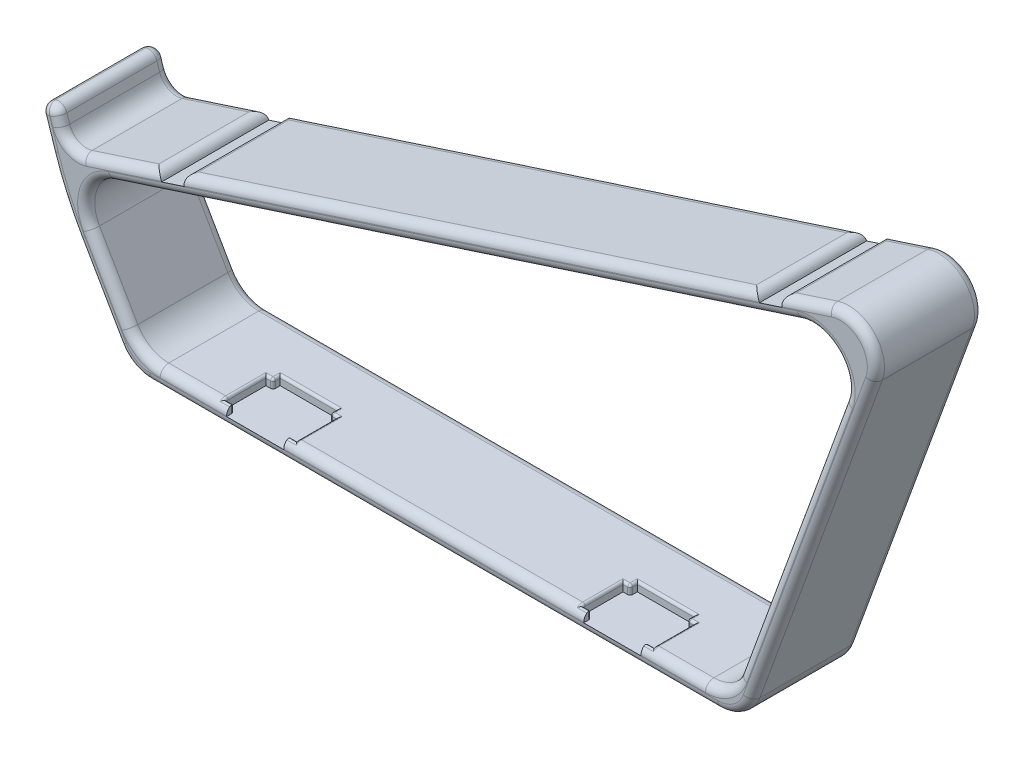
SolidWorks part; units mm, degrees
ref_plane "Front Plane" through (0, 0, 0) normal (0, 0, 1) x (1, 0, 0)
ref_plane "Top Plane" through (0, 0, 0) normal (0, 1, 0) x (1, 0, 0)
ref_plane "Right Plane" through (0, 0, 0) normal (1, 0, 0) x (0, 0, -1)
ref_axis "X Axis" through (0, 0, -132.1637) along (0, 0, 1)
ref_axis "Z Axis" through (0, -24.397, 0) along (0, 1, 0)
ref_axis "Y Axis" through (133.8141, 0, 0) along (-1, 0, 0)
sketch "Sketch13" plane through (0, 0, 0) normal (0, 0, 1) x (1, 0, 0)
  line L0 (-98.9778, 0) -> (72.8295, 0)
  line L1 (72.8295, 0) -> (116.5059, 120)
  line L2 (116.5059, 120) -> (-116.5059, 44.3)
  line L3 (-116.5059, 44.3) -> (-119.5957, 53.8107)
  line L4 (-119.5957, 53.8107) -> (-124.3511, 52.2658)
  line L5 (-124.3511, 52.2658) -> (-118.1715, 33.2444)
  line L6 (-118.1715, 33.2444) -> (-98.9778, 0)
  line L7 (-115.8657, 39.2507) -> (108.3014, 112.0773)
  line L8 (108.3014, 112.0773) -> (69.3284, 5)
  line L9 (69.3284, 5) -> (-96.091, 5)
  line L10 (-96.091, 5) -> (-115.8657, 39.2507)
  line L11 (-8.8901, 79.2618) -> (-7.3452, 74.5065) construction
  line L12 (92.7283, 69.2907) -> (97.4268, 67.5806) construction
  line L13 (33.746, 5) -> (33.746, 0) construction
  line L14 (-110.3349, 19.671) -> (-106.0047, 22.171) construction
  line L15 (116.5059, 120) -> (116.5059, 0) construction
  line L16 (116.5059, 0) -> (72.8295, 0) construction
  line L17 (-116.5059, 44.3) -> (-116.5059, 0) construction
  line L18 (-116.5059, 0) -> (-98.9778, 0) construction
  line L19 (-116.5059, 0) -> (-116.5059, -10.091) construction
  line L20 (-116.5059, -10.091) -> (116.5059, -10.091) construction
  line L21 (116.5059, -10.091) -> (116.5059, 0) construction
  line L22 (0, -10.091) -> (0, 0) construction
  dimension "D2" = 245
  dimension "D3" = 5
  dimension "D4" = 5
  dimension "D5" = 5
  dimension "D6" = 5
  dimension "D7" = 44.3
  dimension "D8" = 120
  dimension "D9" = 110
  dimension "D10" = 5
  dimension "D11" = 120
  dimension "D12" = 10
  dimension "D13" = 20
extrude "Boss-Extrude1" add sketch "Sketch13" along normal blind 30
fillet "Fillet1" radius 10 7 edges at (116.5059, 120, 15) (108.3014, 112.0773, 15) (-115.8657, 39.2507, 15) (-98.9778, 0, 15) (-96.091, 5, 15) (72.8295, 0, 15) (69.3284, 5, 15)
fillet "Fillet2" radius 90 1 edges at (-118.1715, 33.2444, 15)
fillet "Fillet3" radius 2.5 2 edges at (-119.5957, 53.8107, 15) (-124.3511, 52.2658, 15)
fillet "Fillet4" radius 5 1 edges at (-116.5059, 44.3, 15)
fillet "Fillet6" radius 2.4 42 edges at (68.0621, 6.8085, 0) (-13.9956, 5, 0) (-95.3175, 6.3397, 0) (-104.3344, 19.2779, 0) (-110.3665, 37.1397, 0) (-7.659, 74.4045, 0) (99.0859, 103.1784, 0) (86.5063, 52.1958, 0) (-122.3367, 46.0654, 0) (-117.7184, 33.4461, 0) (-107.6527, 15.0254, 0) (-98.2043, 1.3397, 0) (-13.6884, 0, 0) (71.5632, 1.8085, 0) (92.3591, 53.6571, 0) (107.2904, 111.1011, 0) (-7.3717, 79.7551, 0) (-115.5656, 46.1453, 0) (-118.437, 50.2442, 0) (-120.0659, 52.888, 0) (-123.4284, 51.7956, 0) (-95.3175, 6.3397, 30) (-13.9956, 5, 30) (68.0621, 6.8085, 30) (86.5063, 52.1958, 30) (99.0859, 103.1784, 30) (-7.659, 74.4045, 30) (-110.3665, 37.1397, 30) (-104.3344, 19.2779, 30) (107.2904, 111.1011, 30) (92.3591, 53.6571, 30) (71.5632, 1.8085, 30) (-13.6884, 0, 30) (-98.2043, 1.3397, 30) (-107.6527, 15.0254, 30) (-117.7184, 33.4461, 30) (-122.3367, 46.0654, 30) (-123.4284, 51.7956, 30) (-120.0659, 52.888, 30) (-118.437, 50.2442, 30) (-115.5656, 46.1453, 30) (-7.3717, 79.7551, 30)
sketch "Sketch17" plane through (0, 0, 0) normal (0, -1, 0) x (1, 0, 0)
  line L0 (-13.6884, 27.6) -> (-13.6884, 2.4) construction
  line L1 (65.8274, 27.6) -> (-93.2043, 27.6) construction
  line L2 (-93.2043, 2.4) -> (65.8274, 2.4) construction
  line L3 (-76.9543, 15) -> (49.5774, 15) construction
  line L4 (-93.2043, 27.6) -> (-93.2043, 2.4) construction
  line L5 (-89.4543, 2.5) -> (-64.4543, 2.5)
  line L6 (-89.4543, 2.5) -> (-89.4543, 27.5)
  line L7 (-89.4543, 27.5) -> (-64.4543, 27.5)
  line L8 (-64.4543, 2.5) -> (-64.4543, 27.5)
  line L9 (-89.4543, 2.5) -> (-64.4543, 27.5) construction
  line L10 (-89.4543, 27.5) -> (-64.4543, 2.5) construction
  line L11 (37.0774, 2.5) -> (62.0774, 2.5)
  line L12 (37.0774, 2.5) -> (37.0774, 27.5)
  line L13 (37.0774, 27.5) -> (62.0774, 27.5)
  line L14 (62.0774, 2.5) -> (62.0774, 27.5)
  line L15 (37.0774, 2.5) -> (62.0774, 27.5) construction
  line L16 (37.0774, 27.5) -> (62.0774, 2.5) construction
  point P8 (-13.6884, 15)
  point P9 (-13.6884, 15)
  dimension "D1" = 25
  dimension "D2" = 25
  dimension "D3" = 3.75
extrude "Cut-Extrude4" cut sketch "Sketch17" against normal blind 1
sketch "Sketch15" plane through (-24.1407, 74.3073, 0) normal (-0.309, 0.9511, 0) x (0.9511, 0.309, 0)
  line L0 (-97.1173, -2.4) -> (-97.1173, -27.6) construction
  line L1 (-97.1173, -15) -> (-66.6173, -15) construction
  line L2 (127.3807, -30) -> (-92.1173, -30) construction
  line L3 (-69.9673, -30) -> (-63.2673, -30)
  line L4 (-69.9673, -30) -> (-69.9673, 0)
  line L5 (-69.9673, 0) -> (-63.2673, 0)
  line L6 (-63.2673, -30) -> (-63.2673, 0)
  line L7 (-69.9673, -30) -> (-63.2673, 0) construction
  line L8 (-69.9673, 0) -> (-63.2673, -30) construction
  line L9 (-66.6173, -15) -> (109.3827, -15) construction
  line L10 (-92.1173, 0) -> (127.3807, 0) construction
  line L11 (106.0327, -30) -> (112.7327, -30)
  line L12 (106.0327, -30) -> (106.0327, 0)
  line L13 (106.0327, 0) -> (112.7327, 0)
  line L14 (112.7327, -30) -> (112.7327, 0)
  line L15 (106.0327, -30) -> (112.7327, 0) construction
  line L16 (106.0327, 0) -> (112.7327, -30) construction
  dimension "D1" = 30.5
  dimension "D2" = 6.7
  dimension "D3" = 176
extrude "Cut-Extrude2" cut sketch "Sketch15" against normal blind 2.5
sketch "Sketch16" plane through (0, 0, 30) normal (0, 0, 1) x (1, 0, 0)
  line L0 (74.326, 106.2968) -> (75.0985, 103.9191) construction
  line L1 (-84.3122, 54.759) -> (76.7037, 107.0692) construction
  line L2 (75.0985, 103.9191) -> (77.4761, 104.6915) construction
  line L4 (-104.8621, 45.349) -> (88.061, 108.0252) construction
  line L5 (74.326, 106.2968) -> (76.7037, 107.0692)
  line L6 (76.7037, 107.0692) -> (77.4761, 104.6915)
  line L7 (77.4761, 104.6915) -> (83.8483, 106.7617) construction
  line L8 (80.6622, 105.7266) -> (79.8796, 108.1354) construction
  line L9 (83.0758, 109.1394) -> (83.8483, 106.7617)
  line L10 (85.4535, 109.9118) -> (83.0758, 109.1394)
  line L11 (-83.5398, 52.3813) -> (77.4761, 104.6915) construction
  line L12 (-3.0318, 78.5364) -> (-5.2501, 85.3645) construction
  line L13 (-90.6844, 52.6888) -> (-89.9119, 50.3111)
  line L14 (-93.0621, 51.9163) -> (-90.6844, 52.6888)
  line L15 (-81.9346, 55.5314) -> (-84.3122, 54.759)
  line L16 (-84.3122, 54.759) -> (-83.5398, 52.3813)
  arc A0 (74.326, 106.2968) -> (77.4761, 104.6915) centre (75.0985, 103.9191) cw
  arc A1 (85.4535, 109.9118) -> (83.8483, 106.7617) centre (86.226, 107.5341) ccw
  arc A2 (-93.0621, 51.9163) -> (-89.9119, 50.3111) centre (-92.2896, 49.5387) cw
  arc A3 (-81.9346, 55.5314) -> (-83.5398, 52.3813) centre (-81.1621, 53.1537) ccw
  dimension "D1" = 2.5
extrude "Cut-Extrude3" cut sketch "Sketch16" against normal up to surface (30 mm away) up to face at (-33.182, 55.8128, 0)
sketch "Sketch14" plane through (0, 5, 0) normal (0, 1, 0) x (1, 0, 0)
  line L0 (-13.7135, 0) -> (-13.7135, -30) construction
  line L1 (-90.3175, -30) -> (62.3264, -30) construction
  line L2 (-63.7135, -15) -> (36.2865, -15) construction
  line L3 (-63.7135, -15) -> (-63.7135, -30) construction
  line L4 (-73.7135, -30) -> (-53.7135, -30)
  line L5 (-73.7135, -30) -> (-73.7135, -15)
  line L6 (-73.7135, -15) -> (-53.7135, -15)
  line L7 (-53.7135, -30) -> (-53.7135, -15)
  line L8 (-73.7135, -28) -> (-71.7135, -28)
  line L9 (-71.7135, -28) -> (-71.7135, -30)
  line L10 (-73.7135, -22.5) -> (-53.7135, -22.5) construction
  line L11 (-55.7135, -28) -> (-55.7135, -30)
  line L12 (-53.7135, -28) -> (-55.7135, -28)
  line L13 (-53.7135, -17) -> (-55.7135, -17)
  line L14 (-55.7135, -17) -> (-55.7135, -15)
  line L15 (-71.7135, -17) -> (-71.7135, -15)
  line L16 (-73.7135, -17) -> (-71.7135, -17)
  line L17 (28.2865, -17) -> (28.2865, -15)
  line L18 (26.2865, -17) -> (28.2865, -17)
  line L19 (26.2865, -28) -> (28.2865, -28)
  line L20 (28.2865, -28) -> (28.2865, -30)
  line L21 (44.2865, -28) -> (44.2865, -30)
  line L22 (46.2865, -28) -> (44.2865, -28)
  line L23 (44.2865, -17) -> (44.2865, -15)
  line L24 (46.2865, -17) -> (44.2865, -17)
  line L25 (46.2865, -15) -> (26.2865, -15)
  line L26 (26.2865, -30) -> (26.2865, -15)
  line L27 (46.2865, -30) -> (26.2865, -30)
  line L28 (46.2865, -30) -> (46.2865, -15)
  line L29 (-13.7135, 0) -> (0, 0) construction
  point P7 (-13.7135, -15)
  point P8 (-63.7135, -15)
  line M35 (-90.3175, -27.6) -> (62.3264, -27.6)
  dimension "D1" = 0
  dimension "D2" = 20
  dimension "D3" = 2
  dimension "D4" = 100
  dimension "D5" = 30
extrude "Cut-Extrude1" cut sketch "Sketch14" against normal blind 2.5 contours L16 L5 L7 L13 L14 L6 L15 M35 | L28 L24 L23 L25 L17 L18 L26 M35 | L22 L28 L26 L19 L20 L27 L21 M35 | L12 L7 L5 L8 L9 L4 L11 M35 region at (36.2865, 5, 21.4738) region at (36.2865, 5, 28.76) region at (-63.7135, 5, 28.76) region at (-63.7135, 5, 21.4738)
fillet "Fillet5" radius 0.7 30 edges at (46.2865, 5, 22.3) (45.2865, 5, 17) (44.2865, 5, 16) (36.2865, 5, 15) (28.2865, 5, 16) (27.2865, 5, 17) (26.2865, 5, 22.3) (44.2865, 3.7332, 28) (28.2865, 3.7332, 28) (44.2865, 3.75, 17) (28.2865, 3.75, 17) (-71.7135, 3.7332, 28) (-55.7135, 3.7332, 28) (-55.7135, 3.75, 17) (-71.7135, 3.75, 17) (-53.7135, 5, 22.3) (-54.7135, 5, 17) (-55.7135, 5, 16) (-73.7135, 5, 22.3) (-72.7135, 5, 17) (-71.7135, 5, 16) (-63.7135, 5, 15) (-53.7135, 4.9916, 27.8007) (-73.7135, 4.9916, 27.8007) (46.2865, 4.9916, 27.8007) (26.2865, 4.9916, 27.8007) (45.2865, 4.9664, 28) (27.2865, 4.9664, 28) (-54.7135, 4.9664, 28) (-72.7135, 4.9664, 28)
